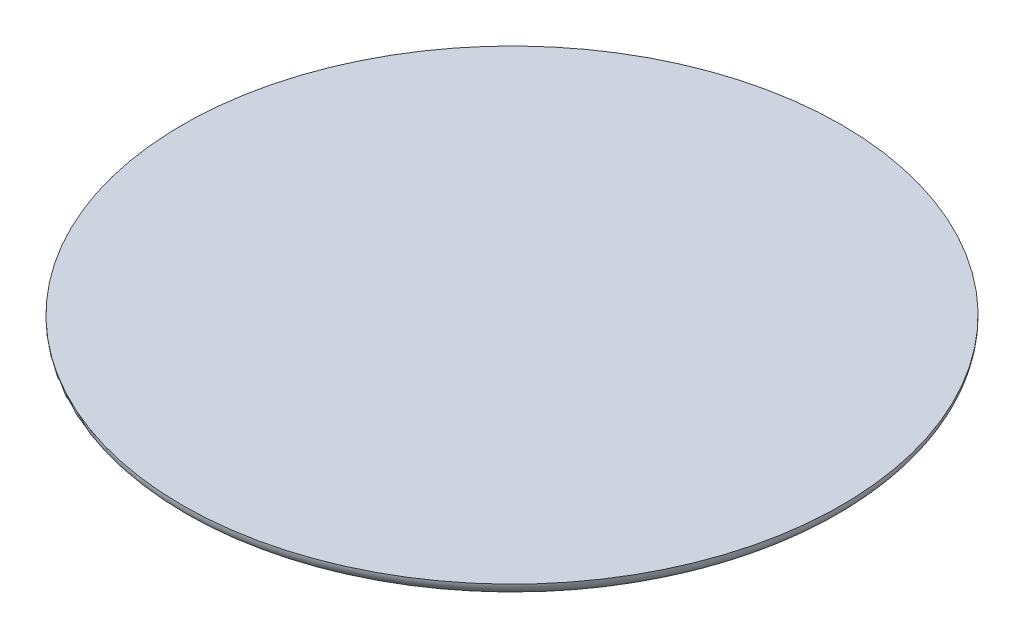
SolidWorks part; units mm, degrees
ref_plane "Front Plane" through (0, 0, 0) normal (0, 0, 1) x (1, 0, 0)
ref_plane "Top Plane" through (0, 0, 0) normal (0, 1, 0) x (1, 0, 0)
ref_plane "Right Plane" through (0, 0, 0) normal (1, 0, 0) x (0, 0, -1)
sketch "Sketch1" plane through (0, 0, 0) normal (0, 1, 0) x (1, 0, 0)
  circle A0 centre (0, 0) radius 50
  dimension "D1" = 100
extrude "Boss-Extrude1" add sketch "Sketch1" along normal blind 2
fillet "Fillet1" radius 2 1 edges at (0, 0, 50)
